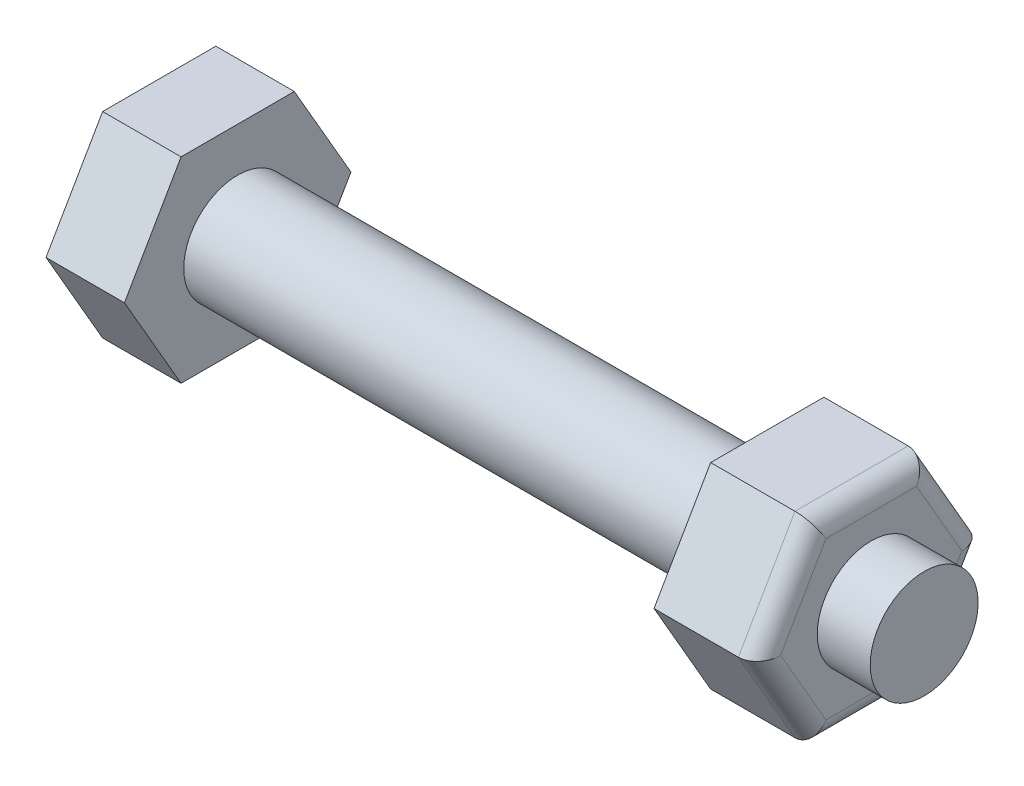
SolidWorks part; units mm, degrees
material "ABS"
ref_plane "Front Plane" through (0, 0, 0) normal (0, 0, 1) x (1, 0, 0)
ref_plane "Top Plane" through (0, 0, 0) normal (0, 1, 0) x (1, 0, 0)
ref_plane "Right Plane" through (0, 0, 0) normal (1, 0, 0) x (0, 0, -1)
sketch "Sketch1" plane through (0, 0, 0) normal (0, 0, 1) x (1, 0, 0)
  line L0 (0, 0) -> (35.941, 0) construction
  line L1 (0, 2.75) -> (35, 2.75)
  line L2 (35, 2.75) -> (35, 0)
  line L3 (35, 0) -> (0, 0)
  line L4 (0, 0) -> (0, 2.75)
  dimension "D1" = 5.5
  dimension "D2" = 35
revolve "Revolve1" add sketch "Sketch1" angle 360 about L0
sketch "Sketch2" plane through (0, 0, 0) normal (1, 0, 0) x (0, 0, -1)
  line L1 (5.7735, 0) -> (2.8868, 5)
  line L2 (2.8868, 5) -> (-2.8868, 5)
  line L3 (-2.8868, 5) -> (-5.7735, 0)
  line L4 (-5.7735, 0) -> (-2.8868, -5)
  line L5 (-2.8868, -5) -> (2.8868, -5)
  line L6 (2.8868, -5) -> (5.7735, 0)
  circle A0 centre (0, 0) radius 5 construction
  dimension "D1" = 10
extrude "Boss-Extrude1" add sketch "Sketch2" against normal blind 4
ref_plane "Plane1" through (27, 0, 0) normal (1, 0, 0) x (0, 0, -1)
sketch "Sketch3" plane through (27, 0, 0) normal (1, 0, 0) x (0, 0, -1)
  line L1 (5.7735, 0) -> (2.8868, 5)
  line L2 (2.8868, 5) -> (-2.8868, 5)
  line L3 (-2.8868, 5) -> (-5.7735, 0)
  line L4 (-5.7735, 0) -> (-2.8868, -5)
  line L5 (-2.8868, -5) -> (2.8868, -5)
  line L6 (2.8868, -5) -> (5.7735, 0)
  circle A0 centre (0, 0) radius 5 construction
  dimension "D1" = 10
extrude "Boss-Extrude2" add sketch "Sketch3" along normal blind 5.3
fillet "Fillet1" radius 1 6 edges at (32.3, 2.5, -4.3301) (32.3, -2.5, -4.3301) (32.3, -5, 0) (32.3, -2.5, 4.3301) (32.3, 2.5, 4.3301) (32.3, 5, 0)
ref_axis "MAIN" through (-5.95, 0, 0) along (1, 0, 0)
ref_plane "MIDLINE" through (13.5, 0, 0) normal (1, 0, 0) x (0, 0, -1)
